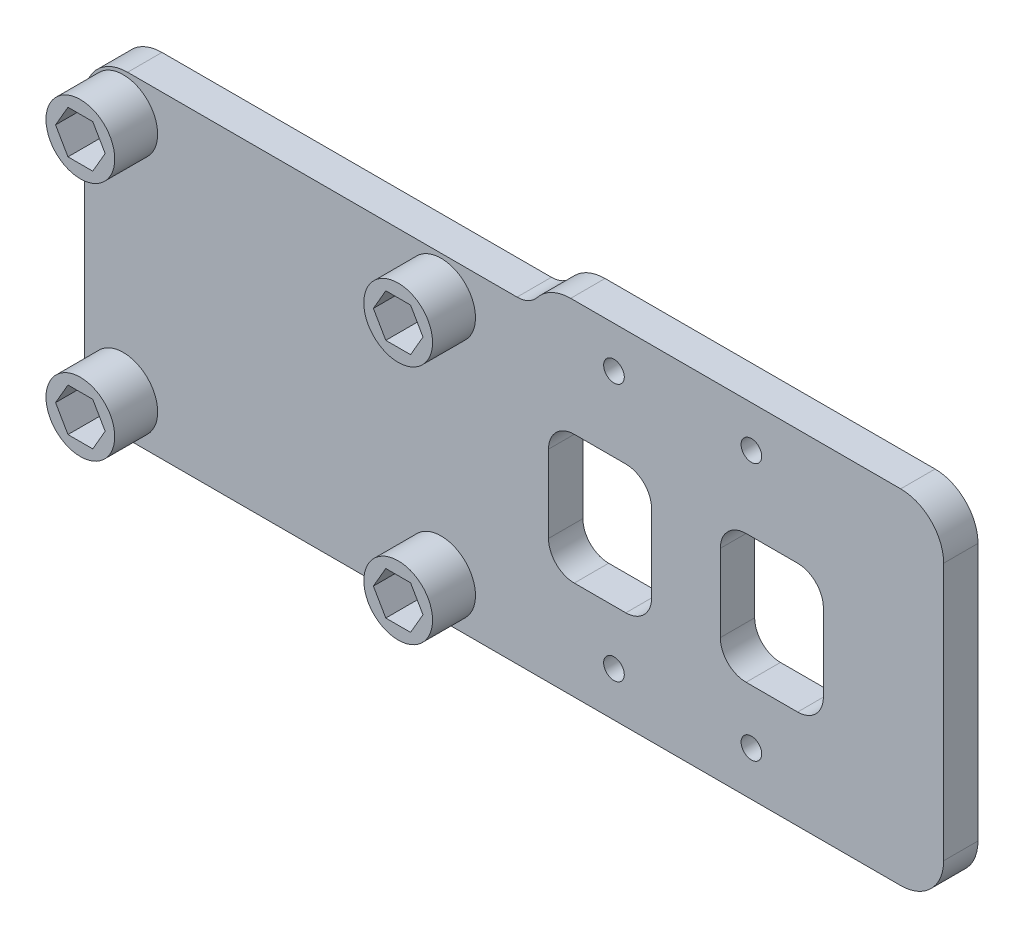
SolidWorks part; units mm, degrees
ref_plane "Front Plane" through (0, 0, 0) normal (0, 0, 1) x (1, 0, 0)
ref_plane "Top Plane" through (0, 0, 0) normal (0, 1, 0) x (1, 0, 0)
ref_plane "Right Plane" through (0, 0, 0) normal (1, 0, 0) x (0, 0, -1)
ref_plane "Plane1" through (0, 0, 34.8116) normal (0, 0, -1) x (-1, 0, 0)
sketch "Sketch1" plane through (0, 0, 34.8116) normal (0, 0, -1) x (-1, 0, 0)
  line L0 (-23.5355, 118.8347) -> (-23.5355, 78.8347)
  line L1 (-23.5355, 78.8347) -> (26.4645, 78.8347)
  line L2 (26.4645, 78.8347) -> (26.4645, 118.8347)
  line L3 (26.4645, 118.8347) -> (-23.5355, 118.8347)
extrude "Boss-Extrude1" add sketch "Sketch1" against normal blind 4
sketch "Sketch2" plane through (0, 0, 38.8116) normal (0, 0, 1) x (1, 0, 0)
  line L0 (23.5355, 90.3347) -> (23.5355, 105.3347)
  line L1 (23.5355, 105.3347) -> (15.5355, 105.3347)
  line L2 (15.5355, 105.3347) -> (15.5355, 90.3347)
  line L3 (15.5355, 90.3347) -> (23.5355, 90.3347)
  line L4 (23.5355, 118.8347) -> (23.5355, 78.8347) construction
  line L6 (15.5355, 105.3347) -> (23.5355, 90.3347) construction
  line L7 (15.5355, 90.3347) -> (23.5355, 105.3347) construction
  line L8 (23.5355, 78.8347) -> (-26.4645, 78.8347) construction
  point P6 (19.5355, 97.8347)
  dimension "D1" = 8
  dimension "D2" = 15
  dimension "D3" = 19
extrude "Cut-Extrude1" cut sketch "Sketch2" against normal through all
sketch "Sketch3" plane through (0, 0, 38.8116) normal (0, 0, 1) x (1, 0, 0)
  line L0 (7.5355, 105.3347) -> (-4.4645, 105.3347)
  line L1 (-4.4645, 105.3347) -> (-4.4645, 90.3347)
  line L2 (-4.4645, 90.3347) -> (7.5355, 90.3347)
  line L3 (7.5355, 90.3347) -> (7.5355, 105.3347)
  line L4 (23.5355, 105.3347) -> (15.5355, 105.3347) construction
  line L5 (15.5355, 90.3347) -> (23.5355, 90.3347) construction
  line L6 (15.5355, 105.3347) -> (15.5355, 90.3347) construction
  dimension "D1" = 8
  dimension "D2" = 12
extrude "Cut-Extrude2" cut sketch "Sketch3" against normal through all
hole_wizard "CBORE for M2 Pan Head Machine Screw1" positions "Sketch5" profile "Sketch4" counterbore size "M2" standard "ANSI Metric" end condition up to next
sketch "Sketch5" plane through (0, 0, 34.8116) normal (0, 0, -1) x (-1, 0, 0)
  point P0 (-3.1566, 84.0163)
  point P1 (-19.1566, 84.0163)
  point P2 (-19.1566, 114.0163)
  point P3 (-3.1566, 114.0163)
sketch "Sketch4" plane through (3.1566, 84.0163, 34.8116) normal (1, 0, 0) x (0, 1, 0)
  line L0 (0, 0) -> (0, 4)
  line L1 (0, 4) -> (1.2, 4)
  line L3 (1.2, 4) -> (1.2, 1.6)
  line L4 (1.2, 1.6) -> (2.5, 1.6)
  line L5 (2.5, 1.6) -> (2.5, 0)
  line L7 (2.5, 0) -> (0, 0)
  line L11 (0, -6.35) -> (0, 107.95) construction
  dimension "Thru Hole Dia." = 2.4
  dimension "Thru Hole Depth" = 4
  dimension "C'Bore Dia." = 5
  dimension "C'Bore Depth" = 1.6
sketch "Sketch6" plane through (0, 0, 38.8116) normal (0, 0, 1) x (1, 0, 0)
  line L0 (-26.4645, 78.8347) -> (-26.4645, 118.8347) construction
  line L1 (-11.4645, 78.8347) -> (-58.4645, 78.8347)
  line L2 (-11.4645, 78.8347) -> (-11.4645, 115.8347)
  line L3 (-11.4645, 115.8347) -> (-58.4645, 115.8347)
  line L4 (-58.4645, 78.8347) -> (-58.4645, 115.8347)
  line L7 (23.5355, 78.8347) -> (-26.4645, 78.8347) construction
  dimension "D1" = 47
  dimension "D2" = 37
  dimension "D3" = 15
extrude "Boss-Extrude2" add sketch "Sketch6" against normal up to surface (4 mm away) up to face at (0.6566, 84.0163, 34.8116)
sketch "Sketch7" plane through (0, 0, 38.8116) normal (0, 0, 1) x (1, 0, 0)
  line L0 (-53.9645, 111.3347) -> (-53.9645, 83.3347) construction
  line L1 (-58.4645, 97.3347) -> (-53.9645, 97.3347) construction
  line L2 (-58.4645, 115.8347) -> (-58.4645, 78.8347) construction
  line L4 (-11.4645, 78.8347) -> (-11.4645, 115.8347) construction
  circle A0 centre (-53.9645, 111.3347) radius 4
  circle A1 centre (-16.9645, 111.3347) radius 4
  circle A2 centre (-53.9645, 83.3347) radius 4
  circle A3 centre (-16.9645, 83.3347) radius 4
  dimension "D3" = 8
  dimension "D1" = 37
  dimension "D2" = 28
  dimension "D4" = 5.5
extrude "Boss-Extrude3" add sketch "Sketch7" along normal blind 5
hole_wizard "Ø2.7 (2.7) Diameter Hole1" positions "Sketch8" profile "Sketch9" hole size "Ø2.7" standard "ANSI Metric"
sketch "Sketch8" plane through (0, 0, 43.8116) normal (0, 0, 1) x (1, 0, 0)
  point P0 (-53.9645, 111.3347)
  point P3 (-16.9645, 111.3347)
  point P6 (-16.9645, 83.3347)
  point P9 (-53.9645, 83.3347)
sketch "Sketch9" plane through (-53.9645, 111.3347, 43.8116) normal (1, 0, 0) x (0, -1, 0)
  line L0 (0, 0) -> (0, 4.8112)
  line L1 (0, 4.8112) -> (1.35, 4)
  line L2 (1.35, 4) -> (1.35, 0)
  line L5 (1.35, 0) -> (0, 0)
  line L10 (0, 4.8112) -> (-1.35, 4) construction
  line L11 (0, -6.35) -> (0, 107.95) construction
  dimension "Hole Dia." = 2.7
  dimension "Hole Depth" = 4
  dimension "Drill Angle" = 118
sketch "Sketch10" plane through (0, 0, 43.8116) normal (0, 0, 1) x (1, 0, 0)
  line L0 (-26.4645, 115.8347) -> (-58.4645, 115.8347) construction
  line L1 (-52.5211, 113.8347) -> (-55.4078, 113.8347)
  line L2 (-55.4078, 113.8347) -> (-56.8512, 111.3347)
  line L3 (-56.8512, 111.3347) -> (-55.4078, 108.8347)
  line L4 (-55.4078, 108.8347) -> (-52.5211, 108.8347)
  line L5 (-52.5211, 108.8347) -> (-51.0777, 111.3347)
  line L6 (-51.0777, 111.3347) -> (-52.5211, 113.8347)
  line L8 (-52.5211, 85.8347) -> (-55.4078, 85.8347)
  line L9 (-55.4078, 85.8347) -> (-56.8512, 83.3347)
  line L10 (-56.8512, 83.3347) -> (-55.4078, 80.8347)
  line L11 (-55.4078, 80.8347) -> (-52.5211, 80.8347)
  line L12 (-52.5211, 80.8347) -> (-51.0777, 83.3347)
  line L13 (-51.0777, 83.3347) -> (-52.5211, 85.8347)
  line L14 (-15.5211, 113.8347) -> (-18.4078, 113.8347)
  line L15 (-18.4078, 113.8347) -> (-19.8512, 111.3347)
  line L16 (-19.8512, 111.3347) -> (-18.4078, 108.8347)
  line L17 (-18.4078, 108.8347) -> (-15.5211, 108.8347)
  line L18 (-15.5211, 108.8347) -> (-14.0777, 111.3347)
  line L19 (-14.0777, 111.3347) -> (-15.5211, 113.8347)
  line L20 (-15.5211, 85.8347) -> (-18.4078, 85.8347)
  line L21 (-18.4078, 85.8347) -> (-19.8512, 83.3347)
  line L22 (-19.8512, 83.3347) -> (-18.4078, 80.8347)
  line L23 (-18.4078, 80.8347) -> (-15.5211, 80.8347)
  line L24 (-15.5211, 80.8347) -> (-14.0777, 83.3347)
  line L25 (-14.0777, 83.3347) -> (-15.5211, 85.8347)
  circle A0 centre (-53.9645, 111.3347) radius 2.5 construction
  circle A1 centre (-53.9645, 83.3347) radius 2.5 construction
  circle A2 centre (-16.9645, 111.3347) radius 2.5 construction
  circle A3 centre (-16.9645, 83.3347) radius 2.5 construction
  dimension "D1" = 5
extrude "Cut-Extrude3" cut sketch "Sketch10" against normal blind 6.5
sketch "Sketch11" plane through (0, 0, 38.8116) normal (0, 0, 1) x (1, 0, 0)
  line L0 (23.5355, 118.8347) -> (41.5355, 118.8347)
  line L1 (41.5355, 118.8347) -> (41.5355, 78.8347)
  line L2 (41.5355, 78.8347) -> (23.5355, 78.8347)
  line L3 (23.5355, 78.8347) -> (23.5355, 90.3347)
  line L4 (23.5355, 90.3347) -> (23.5355, 78.8347) construction
  line L5 (23.5355, 90.3347) -> (27.5355, 90.3347)
  line L6 (27.5355, 90.3347) -> (27.5355, 105.3347)
  line L7 (27.5355, 105.3347) -> (23.5355, 105.3347)
  line L8 (23.5355, 105.3347) -> (23.5355, 118.8347)
  line L9 (23.5355, 78.8347) -> (-58.4645, 78.8347) construction
  line L10 (23.5355, 105.3347) -> (15.5355, 105.3347) construction
  line L11 (15.5355, 90.3347) -> (23.5355, 90.3347) construction
  line L12 (15.5355, 105.3347) -> (15.5355, 90.3347) construction
  line L13 (-58.4645, 115.8347) -> (-58.4645, 78.8347) construction
  dimension "D1" = 12
  dimension "D2" = 100
extrude "Boss-Extrude4" add sketch "Sketch11" against normal up to surface (4 mm away) up to face at (-4.4645, 101.8347, 34.8116)
sketch "Sketch12" plane through (0, 0, 38.8116) normal (0, 0, 1) x (1, 0, 0)
  line L0 (-26.4645, 115.8347) -> (-6.4645, 115.8347)
  line L1 (-6.4645, 115.8347) -> (-6.4645, 118.8347)
  line L2 (-26.4645, 118.8347) -> (41.5355, 118.8347) construction
  line L3 (-6.4645, 118.8347) -> (-26.4645, 118.8347)
  line L4 (-26.4645, 118.8347) -> (-26.4645, 115.8347)
  dimension "D1" = 20
extrude "Cut-Extrude4" cut sketch "Sketch12" against normal blind 10
sketch "Sketch13" plane through (0, 0, 34.8116) normal (0, 0, 1) x (1, 0, 0)
  line L3 (41.5355, 78.8347) -> (41.5355, 118.8347) construction
  line L4 (36.5355, 110.8347) -> (-53.4645, 110.8347) construction
  line L5 (36.5355, 110.8347) -> (36.5355, 83.8347) construction
  line L6 (36.5355, 83.8347) -> (-53.4645, 83.8347) construction
  line L7 (-53.4645, 110.8347) -> (-53.4645, 83.8347) construction
  line L8 (41.5355, 78.8347) -> (-58.4645, 78.8347) construction
  line L9 (-58.4645, 115.8347) -> (-58.4645, 78.8347) construction
  line L10 (-58.4645, 97.3347) -> (-53.4645, 97.3347) construction
  line L11 (-8.4645, 78.8347) -> (-8.4645, 83.8347) construction
  line L12 (36.5355, 110.8347) -> (-53.4645, 83.8347) construction
  line L13 (36.5355, 83.8347) -> (-53.4645, 110.8347) construction
  circle A4 centre (36.5355, 110.8347) radius 2.6
  circle A5 centre (36.5355, 83.8347) radius 2.6
  circle A6 centre (-53.4645, 110.8347) radius 2.6
  circle A7 centre (-53.4645, 83.8347) radius 2.6
  circle A8 centre (-8.4645, 97.3347) radius 2.6
  point P20 (0, 0)
  dimension "D1" = 5
  dimension "D2" = 5
  dimension "D3" = 5.2
extrude "Cut-Extrude5" cut sketch "Sketch13" along normal blind 2.2
sketch "Sketch14" plane through (0, 0, 34.8116) normal (0, 0, -1) x (-1, 0, 0)
  line L0 (-41.5355, 78.8347) -> (-41.5355, 118.8347) construction
  line L1 (-41.5355, 105.8347) -> (-31.5355, 105.8347)
  line L2 (-41.5355, 105.8347) -> (-41.5355, 115.8347) construction
  line L3 (-41.5355, 115.8347) -> (-31.5355, 115.8347)
  line L4 (-31.5355, 105.8347) -> (-31.5355, 115.8347)
  line L5 (-41.5355, 105.8347) -> (-31.5355, 115.8347) construction
  line L6 (-41.5355, 115.8347) -> (-31.5355, 105.8347) construction
  line L7 (-41.5355, 115.8347) -> (-41.5355, 118.8347)
  line L8 (6.4645, 118.8347) -> (-41.5355, 118.8347) construction
  line L9 (-41.5355, 118.8347) -> (6.4645, 118.8347)
  line L10 (6.4645, 118.8347) -> (6.4645, 115.8347)
  line L11 (6.4645, 115.8347) -> (58.4645, 115.8347)
  line L12 (58.4645, 115.8347) -> (58.4645, 78.8347)
  line L13 (58.4645, 78.8347) -> (-41.5355, 78.8347)
  line L14 (-41.5355, 78.8347) -> (-41.5355, 105.8347)
  circle A0 centre (-36.5355, 110.8347) radius 2.6 construction
  point P0 (-36.5355, 110.8347)
extrude "Cut-Extrude6" [suppressed] cut sketch "Sketch14" against normal up to next
fillet "Fillet1" radius 5 5 edges at (-58.4645, 115.8347, 36.8116) (-58.4645, 78.8347, 36.8116) (41.5355, 78.8347, 36.8116) (41.5355, 118.8347, 36.8116) (-6.4645, 118.8347, 36.8116)
fillet "Fillet2" radius 3 8 edges at (7.5355, 90.3347, 36.8116) (-4.4645, 90.3347, 36.8116) (15.5355, 90.3347, 36.8116) (27.5355, 90.3347, 36.8116) (15.5355, 105.3347, 36.8116) (7.5355, 105.3347, 36.8116) (-4.4645, 105.3347, 36.8116) (27.5355, 105.3347, 36.8116)
fillet "Fillet3" radius 3 1 edges at (-6.4645, 115.8347, 36.8116)
